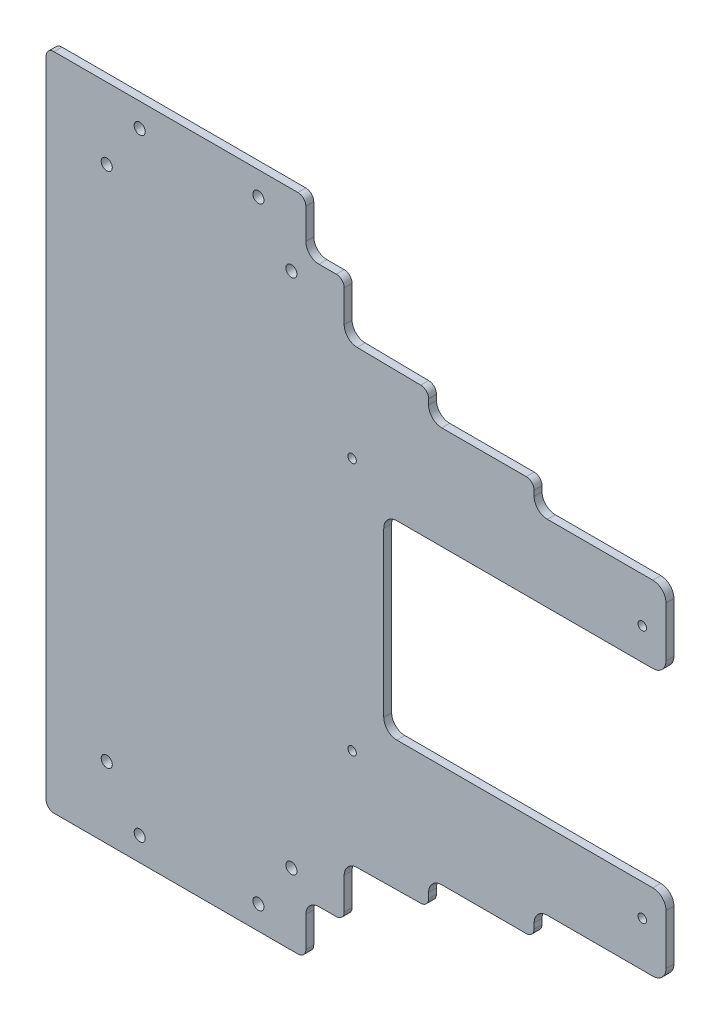
SolidWorks part; units mm, degrees
material "Thornel Mat VMA"
ref_plane "前视基准面" through (0, 0, 0) normal (0, 0, 1) x (1, 0, 0)
ref_plane "上视基准面" through (0, 0, 0) normal (0, 1, 0) x (1, 0, 0)
ref_plane "右视基准面" through (0, 0, 0) normal (1, 0, 0) x (0, 0, -1)
sketch "草图1" plane through (0, 0, 0) normal (0, 0, 1) x (1, 0, 0)
  line L1 (-117.5, -125) -> (117.5, -125)
  line L2 (-117.5, -125) -> (-117.5, 125)
  line L3 (-117.5, 125) -> (117.5, 125)
  line L4 (117.5, -125) -> (117.5, 125)
  line L5 (-117.5, -125) -> (117.5, 125) construction
  line L6 (-117.5, 125) -> (117.5, -125) construction
  point P0 (0, 0)
  dimension "D1" = 235
  dimension "D2" = 250
extrude "凸台-拉伸1" add sketch "草图1" along normal blind 3
sketch "草图2" plane through (0, 0, 3) normal (0, 0, 1) x (1, 0, 0)
  line L1 (117.5, 36) -> (10.5, 36)
  line L2 (117.5, 36) -> (117.5, -36)
  line L3 (117.5, -36) -> (10.5, -36)
  line L4 (10.5, 36) -> (10.5, -36)
  line L5 (117.5, 36) -> (10.5, -36) construction
  line L6 (117.5, -36) -> (10.5, 36) construction
  line L7 (117.5, -125) -> (117.5, 125) construction
  point P0 (64, 0)
  dimension "D1" = 72
  dimension "D2" = 107
extrude "切除-拉伸1" cut sketch "草图2" against normal through all
sketch "草图3" plane through (0, 0, 3) normal (0, 0, 1) x (1, 0, 0)
  line L0 (117.5, 125) -> (-117.5, 125) construction
  line L1 (-117.5, 125) -> (-117.5, -125) construction
  circle A0 centre (-94.5, 98) radius 2.1
  circle A1 centre (-24.5, 98) radius 2.1
  dimension "D1" = 4.2
  dimension "D2" = 70
  dimension "D3" = 27
  dimension "D4" = 23
extrude "切除-拉伸2" cut sketch "草图3" against normal blind 10
mirror "镜向1" about plane through (0, 0, 0) normal (0, 1, 0) of "切除-拉伸2"
sketch "草图4" plane through (0, 0, 3) normal (0, 0, 1) x (1, 0, 0)
  line L0 (117.5, 36) -> (117.5, 125) construction
  line L1 (117.5, 36) -> (10.5, 36) construction
  circle A0 centre (108.5, 48) radius 1.6
  circle A1 centre (-1.5, 48) radius 1.6
  circle A2 centre (108.5, -48) radius 1.6
  circle A3 centre (-1.5, -48) radius 1.6
  dimension "D1" = 3.2
  dimension "D2" = 9
  dimension "D3" = 12
  dimension "D4" = 2
  dimension "D5" = 2
extrude "切除-拉伸3" cut sketch "草图4" against normal blind 3
sketch "草图5" plane through (0, 0, 3) normal (0, 0, 1) x (1, 0, 0)
  line L0 (117.5, 125) -> (-117.5, 125) construction
  line L1 (117.5, 125) -> (27.5, 125)
  line L2 (117.5, 36) -> (117.5, 125) construction
  line L3 (117.5, 65) -> (117.5, 125)
  line L4 (67.5, 65) -> (67.5, 75)
  line L5 (67.5, 75) -> (27.5, 75)
  line L6 (27.5, 75) -> (27.5, 85)
  line L7 (67.5, 65) -> (117.5, 65)
  line L8 (-4.4966, 105.4469) -> (-4.4969, 85.4469)
  line L9 (117.5, 125) -> (-117.5, 125) construction
  line L10 (67.5, 75) -> (-117.5, 75) construction
  line L11 (67.5, 36) -> (67.5, 75) construction
  line L12 (117.5, 36) -> (117.5, 125) construction
  line L13 (-4.4969, 85.4469) -> (27.5, 85)
  line L14 (-4.0259, 125) -> (27.5, 125)
  line L15 (-19.0259, 125) -> (-19.0259, 105.4469)
  line L16 (-19.0259, 105.4469) -> (-4.4966, 105.4469)
  line L17 (-4.0259, 125) -> (-19.0259, 125)
  dimension "D2" = 90
  dimension "D3" = 60
  dimension "D4" = 32
  dimension "D5" = 10
  dimension "D6" = 15
  dimension "D7" = 20
  dimension "D1" = 50
extrude "切除-拉伸4" cut sketch "草图5" against normal through all
mirror "镜向2" about plane through (0, 0, 0) normal (0, 1, 0) of "切除-拉伸4"
sketch "草图6" plane through (0, 0, 3) normal (0, 0, 1) x (1, 0, 0)
  line L0 (-82, -116) -> (-37, -116) construction
  line L1 (-117.5, -125) -> (-19.0259, -125) construction
  line L2 (-117.5, 125) -> (-117.5, -125) construction
  circle A0 centre (-82, -116) radius 2.1
  circle A1 centre (-37, -116) radius 2.1
  dimension "D3" = 4.2
  dimension "D1" = 45
  dimension "D2" = 9
  dimension "D4" = 35.5
extrude "切除-拉伸5" cut sketch "草图6" against normal blind 3 contours A0 | A1 region at (-82, -116, 3) region at (-37, -116, 3)
mirror "镜向3" about plane through (0, 0, 0) normal (0, 1, 0) of "切除-拉伸5"
fillet "圆角1" radius 5 14 edges at (10.5, -36, 1.5) (10.5, 36, 1.5) (-4.4969, -85.4469, 1.5) (27.5, -75, 1.5) (67.5, -65, 1.5) (67.5, 65, 1.5) (27.5, 75, 1.5) (-4.4969, 85.4469, 1.5) (117.5, -65, 1.5) (117.5, -36, 1.5) (117.5, 36, 1.5) (117.5, 65, 1.5) (-19.0259, 105.4469, 1.5) (-19.0259, -105.4469, 1.5)
fillet "圆角2" radius 3 10 edges at (-117.5, 125, 1.5) (67.5, 75, 1.5) (27.5, 85, 1.5) (-117.5, -125, 1.5) (27.5, -85, 1.5) (67.5, -75, 1.5) (-19.0259, -125, 1.5) (-4.4966, -105.4469, 1.5) (-19.0259, 125, 1.5) (-4.4966, 105.4469, 1.5)
